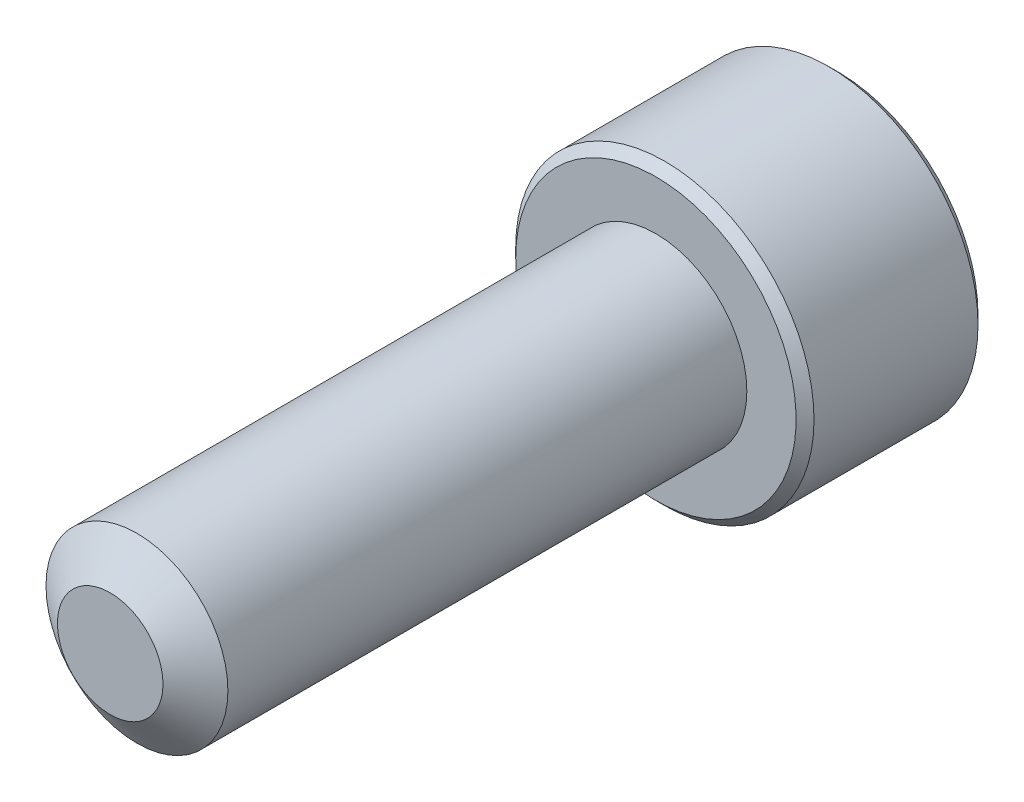
SolidWorks part; units mm, degrees
ref_plane "Front Plane" through (0, 0, 0) normal (0, 0, 1) x (1, 0, 0)
ref_plane "Top Plane" through (0, 0, 0) normal (0, 1, 0) x (1, 0, 0)
ref_plane "Right Plane" through (0, 0, 0) normal (1, 0, 0) x (0, 0, -1)
sketch "Sketch1" plane through (0, 0, 0) normal (0, 0, 1) x (1, 0, 0)
  circle A0 centre (0, 0) radius 1.5875
  dimension "OD" = 3.175
extrude "Extrude1" add sketch "Sketch1" against normal blind 9.525
sketch "Sketch2" plane through (0, 0, 0) normal (0, 0, 1) x (1, 0, 0)
  circle A0 centre (0, 0) radius 1.5875 construction
  circle A1 centre (0, 0) radius 1.5875
curve "Helix/Spiral1" [suppressed] pitch 0.635 height 10.16 turns 16 parameters "pitch"=0.635
sketch "Sketch3" plane through (0, 0, 0) normal (1, 0, 0) x (0, 0, -1)
  line L0 (-0.5556, 1.5875) -> (-0.3175, 1.1751)
  line L1 (-0.3175, 1.1751) -> (-0.2381, 1.1751)
  line L2 (-0.2381, 1.1751) -> (0, 1.5875)
  line L3 (-0.5556, 1.5875) -> (0, 1.5875)
  line L4 (-0.2778, 1.5875) -> (-0.2778, 1.1751) construction
  line L5 (-0.4366, 1.3813) -> (-0.1191, 1.3813) construction
  line L6 (0, 1.5875) -> (0, -1.5875) construction
  line L7 (0, -1.5875) -> (9.525, -1.5875) construction
  point P11 (2.8575, -1.5875)
  dimension "D1" = 0.0794
  dimension "D2" = 0.3175
  dimension "D3" = 60
  dimension "D4" = 2.8575
sweep "Cut-Sweep1" [suppressed] cut profiles "Sketch3" path "Helix/Spiral1"
sketch "Sketch4" plane through (0, 0, 0) normal (1, 0, 0) x (0, 0, -1)
  line L0 (0.4666, 1.5875) -> (0, 0.9211)
  line L1 (0, 0.9211) -> (0, 1.5875)
  line L2 (0.4666, 1.5875) -> (0, 1.5875)
  line L3 (-0.5556, 1.5875) -> (0, 1.5875) construction
  line L4 (0, 0) -> (7.0209, 0) construction
  dimension "D1" = 55
  dimension "D2" = 0.254
revolve "Cut-Revolve1" cut sketch "Sketch4" angle 360 about L4
sketch "Sketch5" [suppressed] plane through (0, 0, 0) normal (1, 0, 0) x (0, 0, -1)
  line L0 (9.525, -1.1864) -> (9.525, 1.1327) construction
  line L1 (9.525, 1.5875) -> (0.1204, 1.5875)
  line L2 (9.525, 1.5875) -> (9.525, 0)
  line L3 (9.525, 0) -> (0.0003, 0)
  line L4 (0.0003, 1.2573) -> (0.0003, 0)
  line L5 (0.1204, 1.5875) -> (0.0003, 1.2573)
  line L6 (0, 0) -> (9.9695, 0) construction
  point P3 (0.0003, 1.5875)
  point P10 (0.0003, 1.5875)
  dimension "D1" = 0.3302
  dimension "Thread min" = 0.0003
  dimension "D3" = 20
revolve "partially thread" [suppressed] add sketch "Sketch5" angle 360 about L6
sketch "Sketch6" plane through (0, 0, -9.525) normal (0, 0, -1) x (-1, 0, 0)
  circle A0 centre (0, 0) radius 2.6035
  dimension "head dia" = 5.207
extrude "Extrude2" add sketch "Sketch6" along normal blind 3.175
sketch "Sketch7" plane through (0, 0, -12.7) normal (0, 0, -1) x (-1, 0, 0)
  line L1 (0, 1.3748) -> (-1.1906, 0.6874)
  line L2 (-1.1906, 0.6874) -> (-1.1906, -0.6874)
  line L3 (-1.1906, -0.6874) -> (0, -1.3748)
  line L4 (0, -1.3748) -> (1.1906, -0.6874)
  line L5 (1.1906, -0.6874) -> (1.1906, 0.6874)
  line L6 (1.1906, 0.6874) -> (0, 1.3748)
  circle A0 centre (0, 0) radius 1.1906 construction
  dimension "hex dia" = 2.3813
extrude "Cut-Extrude1" cut sketch "Sketch7" against normal blind 1.7859
sketch "Sketch8" plane through (0, 0, -12.7) normal (0, 0, -1) x (-1, 0, 0)
  circle A0 centre (0, 0) radius 1.3748
extrude "Cut-Extrude2" cut sketch "Sketch8" against normal through all draft 45
chamfer "Chamfer1" distance 0.1562 angle 45 2 edges at (-2.6035, 0, -12.7) (-2.6035, 0, -9.525)
sketch "Sketch9" plane through (0, 0, 0) normal (1, 0, 0) x (0, 0, -1)
  line L0 (0, 1.5875) -> (0, -1.5875) construction
  line L1 (3.4925, 1.5875) -> (3.4925, -1.5875) construction
  dimension "D1" = 3.4925
sketch "Sketch10" plane through (0, 0, 0) normal (1, 0, 0) x (0, 0, -1)
  line L0 (9.525, 1.5875) -> (9.525, 0)
  line L1 (9.525, 1.5875) -> (9.3663, 1.5875)
  line L2 (9.3663, 1.5875) -> (8.7087, 0)
  line L3 (9.525, 0) -> (8.7087, 0)
  line L4 (9.525, 2.4473) -> (9.525, -2.4473) construction
  dimension "D1" = 22.5
  dimension "D2" = 0.1588
revolve "Revolve1" [suppressed] add sketch "Sketch10" angle 360 about L3
surface "Surface-Knit1" [suppressed]
sketch "Sketch11" plane through (0, 0, 0) normal (1, 0, 0) x (0, 0, -1)
  ellipse E0 centre (3.4925, 0) end of major axis (2.2225, 0) minor radius 0.8731
  dimension "D1" = 1.7463
  dimension "D2" = 2.54
  dimension "D3" = 2.2225
delete or keep bodies "Body-Delete1" [suppressed] type delete bodies bodies 109
surface "Surface-Offset1" [suppressed] parameters "D1"=0.0333
extrude "Boss-Extrude1" [suppressed] add sketch "Sketch11" against normal up to surface (1.3794 mm away)
delete or keep bodies "Body-Delete2" [suppressed] type delete bodies bodies 111
equation "\"D3@Helix/Spiral1\" = \"screw length@Extrude1\"+\"pitch@Helix/Spiral1\""
equation "\"D1@Sketch3\" = \"pitch@Helix/Spiral1\"*.125"
equation "\"D2@Sketch3\" = \"pitch@Helix/Spiral1\"*.5"
equation "\"D1@Cut-Extrude1\" = \"hex dia@Sketch7\"*.75"
equation "\"D1@Chamfer1\" = \"head dia@Sketch6\"*.03"
equation "\"D1@Sketch9\" = \"pitch@Helix/Spiral1\"*5.5"
equation "\"D2@Sketch10\" = \"pitch@Helix/Spiral1\"*.25"
equation "\"D1@Sketch11\" = \"OD@Sketch1\"*.55"
equation "\"D2@Sketch11\" = \"OD@Sketch1\"*.80"
equation "\"D3@Sketch11\" = \"pitch@Helix/Spiral1\"*3.50"
equation "\"D4@Sketch3\" = \"pitch@Helix/Spiral1\"*4.50"
